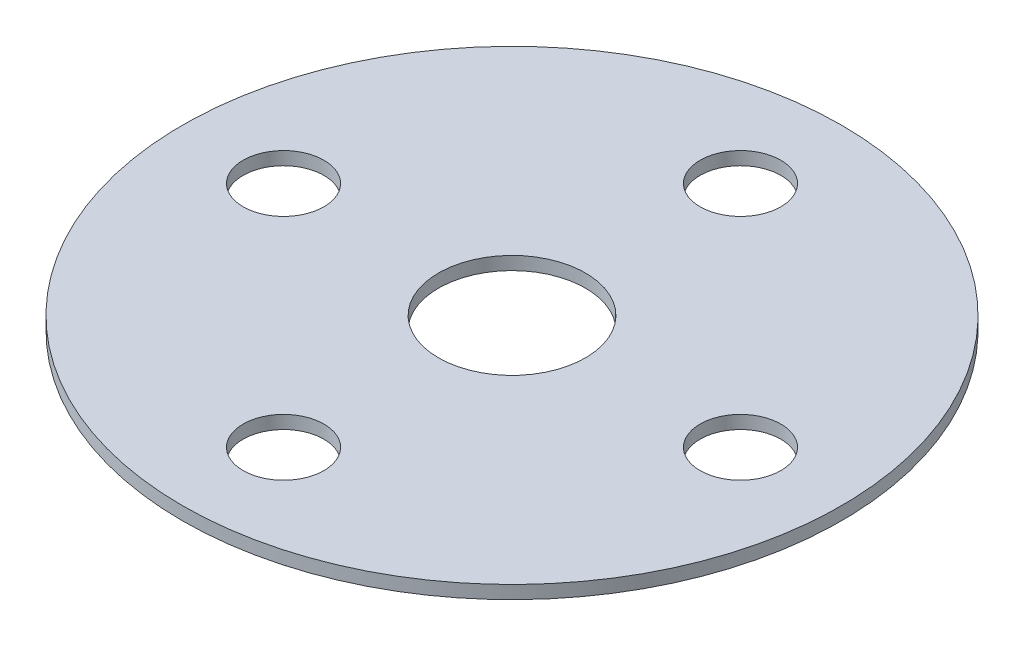
SolidWorks part; units mm, degrees
ref_plane "Front Plane" through (0, 0, 0) normal (0, 0, 1) x (1, 0, 0)
ref_plane "Top Plane" through (0, 0, 0) normal (0, 1, 0) x (1, 0, 0)
ref_plane "Right Plane" through (0, 0, 0) normal (1, 0, 0) x (0, 0, -1)
sketch "Sketch1" plane through (0, 0, 0) normal (0, 1, 0) x (1, 0, 0)
  circle A0 centre (0, 0) radius 21.6364
  circle A1 centre (0, 0) radius 4.826
  circle A2 centre (0, 15) radius 2.65
  circle A3 centre (15, 0) radius 2.65
  circle A4 centre (0, -15) radius 2.65
  circle A5 centre (-15, 0) radius 2.65
  point P6 (-25.7856, -6.6379)
  point P7 (0, 0)
  point P15 (0, 0)
  dimension "D1" = 43.2728
  dimension "D2" = 9.652
  dimension "D3" = 5.3
  dimension "D4" = 15
  dimension "D5" = 4
extrude "Boss-Extrude1" add sketch "Sketch1" along normal blind 0.8636
